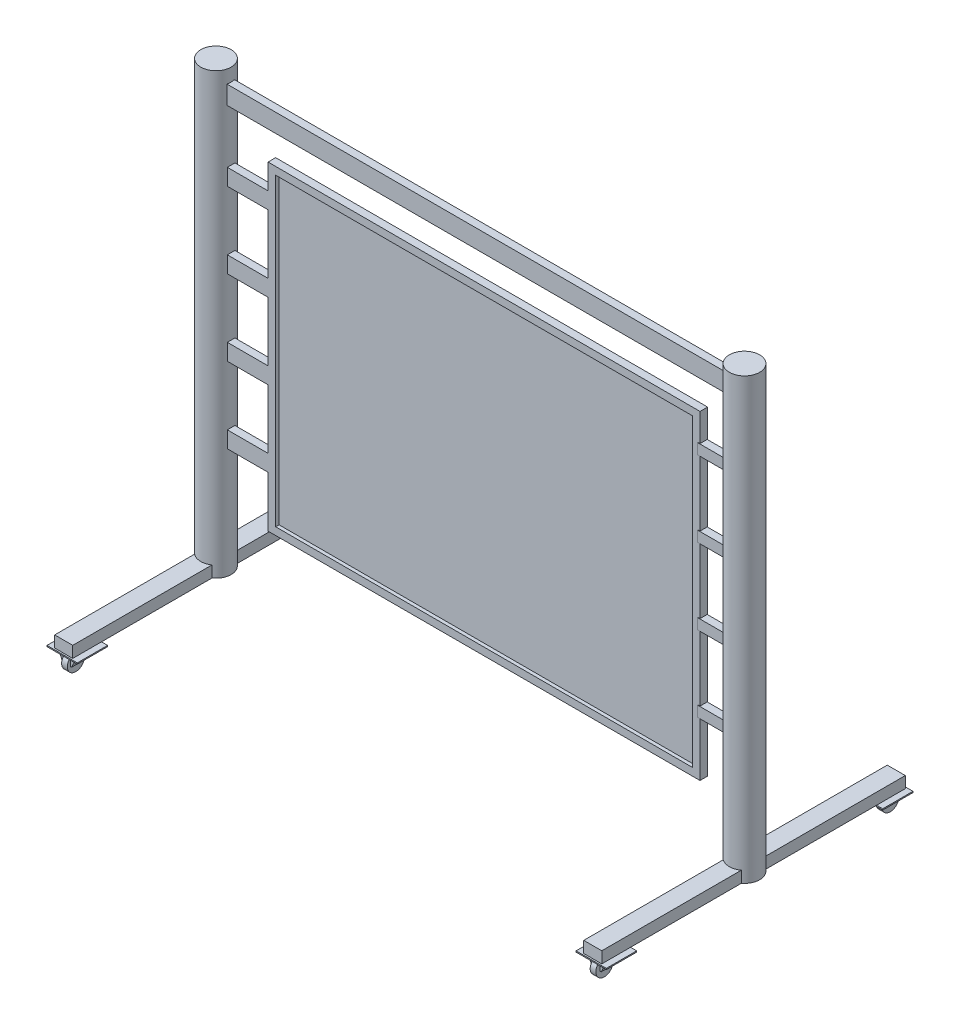
SolidWorks part; units mm, degrees
ref_plane "Alzado" through (0, 0, 0) normal (0, 0, 1) x (1, 0, 0)
ref_plane "Planta" through (0, 0, 0) normal (0, 1, 0) x (1, 0, 0)
ref_plane "Vista lateral" through (0, 0, 0) normal (1, 0, 0) x (0, 0, -1)
sketch "Croquis1" plane through (0, 0, 0) normal (0, 1, 0) x (1, 0, 0)
  line L0 (-40, 0) -> (1435, 0) construction
  circle A0 centre (0, 0) radius 40
  circle A1 centre (1395, 0) radius 40
  dimension "D1" = 80
  dimension "D2" = 80
  dimension "D3" = 1475
extrude "Saliente-Extruir1" add sketch "Croquis1" along normal blind 1160
sketch "Croquis2" plane through (0, 0, 0) normal (0, 0, 1) x (1, 0, 0)
  line L0 (0, 0) -> (0, 1160) construction
  line L1 (40, 1160) -> (-40, 1160) construction
  line L2 (0, 1160) -> (0, 580) construction
  line L3 (0, 580) -> (1435, 580) construction
  line L4 (1435, 0) -> (1435, 1160) construction
  line L5 (147.4875, 1001.8331) -> (147.4875, 158.1669)
  line L6 (167.4875, 981.8331) -> (1267.5125, 981.8331)
  line L7 (167.4875, 981.8331) -> (167.4875, 178.1669)
  line L8 (167.4875, 178.1669) -> (1267.5125, 178.1669)
  line L9 (1267.5125, 981.8331) -> (1267.5125, 178.1669)
  line L10 (147.4875, 158.1669) -> (1287.5125, 158.1669)
  line L11 (1287.5125, 1001.8331) -> (1287.5125, 158.1669)
  line L12 (147.4875, 1001.8331) -> (1287.5125, 1001.8331)
  point P5 (717.5, 580)
  dimension "D1" = 20
extrude "Saliente-Extruir2" add sketch "Croquis2" along normal blind 10 and the other way blind 10 separate body
sketch "Croquis3" plane through (0, 0, 0) normal (0, 0, 1) x (1, 0, 0)
  line L0 (40, 1101.4893) -> (1348.6676, 1101.4893) construction
  line L1 (40, 0) -> (40, 1160) construction
  line L2 (1348.6676, 1101.4893) -> (694.3338, 1101.4893) construction
  line L3 (1355, 1160) -> (1355, 0) construction
  line L4 (33.6676, 1125.7465) -> (1355, 1125.7465)
  line L5 (33.6676, 1125.7465) -> (33.6676, 1077.2322)
  line L6 (33.6676, 1077.2322) -> (1355, 1077.2322)
  line L7 (1355, 1125.7465) -> (1355, 1077.2322)
  line L8 (33.6676, 1125.7465) -> (1355, 1077.2322) construction
  line L9 (33.6676, 1077.2322) -> (1355, 1125.7465) construction
extrude "Saliente-Extruir3" add sketch "Croquis3" along normal blind 10 and the other way blind 10
sketch "Croquis4" plane through (0, 0, 0) normal (0, 0, 1) x (1, 0, 0)
  line L0 (167.4875, 580) -> (1267.5125, 580) construction
  line L1 (167.4875, 981.8331) -> (167.4875, 178.1669) construction
  line L2 (1267.5125, 178.1669) -> (1267.5125, 981.8331) construction
  line L3 (1267.5125, 580) -> (717.5, 580) construction
  line L4 (717.5, 580) -> (717.5, 981.8331) construction
  line L5 (1267.5125, 981.8331) -> (167.4875, 981.8331) construction
  line L7 (167.4875, 981.8331) -> (1267.5125, 981.8331)
  line L8 (167.4875, 981.8331) -> (167.4875, 178.1669)
  line L9 (167.4875, 178.1669) -> (1267.5125, 178.1669)
  line L10 (1267.5125, 981.8331) -> (1267.5125, 178.1669)
  line L11 (167.4875, 981.8331) -> (1267.5125, 178.1669) construction
  line L12 (167.4875, 178.1669) -> (1267.5125, 981.8331) construction
extrude "Saliente-Extruir4" add sketch "Croquis4" along normal blind 1
sketch "Croquis5" plane through (0, 0, 0) normal (0, 1, 0) x (1, 0, 0)
  line L0 (696.8649, -10) -> (696.8649, -155.1745) construction
  line L1 (1418.811, 400.5263) -> (1371.189, 400.5263)
  line L2 (1418.811, 400.5263) -> (1418.811, -400.5263)
  line L3 (1418.811, -400.5263) -> (1371.189, -400.5263)
  line L4 (1371.189, 400.5263) -> (1371.189, -400.5263)
  line L5 (1418.811, 400.5263) -> (1371.189, -400.5263) construction
  line L6 (1418.811, -400.5263) -> (1371.189, 400.5263) construction
  line L7 (1355, -10) -> (38.7298, -10) construction
  line L8 (-25.0811, -400.5263) -> (22.5408, 400.5263) construction
  line L9 (-25.0811, 400.5263) -> (22.5408, -400.5263) construction
  line L10 (22.5408, 400.5263) -> (22.5408, -400.5263)
  line L11 (-25.0811, -400.5263) -> (22.5408, -400.5263)
  line L12 (-25.0811, 400.5263) -> (-25.0811, -400.5263)
  line L13 (-25.0811, 400.5263) -> (22.5408, 400.5263)
  point P0 (1395, 0)
  point P14 (-1.2702, 0)
extrude "Saliente-Extruir5" add sketch "Croquis5" along normal blind 30
sketch "Croquis7" plane through (0, 0, 0) normal (0, 0, 1) x (1, 0, 0)
  line L0 (40, 914.3498) -> (147.4875, 914.3498) construction
  line L1 (40, 0) -> (40, 1077.2322) construction
  line L2 (147.4875, 1001.8331) -> (147.4875, 158.1669) construction
  line L3 (147.4875, 914.3498) -> (93.7438, 914.3498) construction
  line L5 (40, 935.9929) -> (147.4875, 935.9929)
  line L6 (40, 935.9929) -> (40, 892.7068)
  line L7 (40, 892.7068) -> (147.4875, 892.7068)
  line L8 (147.4875, 935.9929) -> (147.4875, 892.7068)
  line L9 (40, 935.9929) -> (147.4875, 892.7068) construction
  line L10 (40, 892.7068) -> (147.4875, 935.9929) construction
extrude "Saliente-Extruir6" add sketch "Croquis7" along normal blind 10 and the other way blind 10
pattern_linear "MatrizL1" count 4 spacing 200 along (0, -1, 0) of "Saliente-Extruir6"
sketch "Croquis11" plane through (0, 0, 1) normal (0, 0, 1) x (1, 0, 0)
  line L0 (147.4875, 935.9929) -> (147.4875, 892.7068)
  line L1 (147.4875, 892.7068) -> (147.4875, 935.9929)
  line L2 (147.4875, 914.3498) -> (1355, 914.3498)
  line L3 (1355, 1160) -> (1355, 0) construction
  line L4 (1355, 914.3498) -> (1282.1767, 914.3498)
  line L5 (1282.1767, 914.3498) -> (1318.5884, 914.3498)
  line L6 (1318.5884, 914.3498) -> (1318.5884, 1077.2322)
  line L7 (38.7298, 1077.2322) -> (1355, 1077.2322) construction
  line L9 (1282.1767, 928.3164) -> (1355, 928.3164)
  line L10 (1282.1767, 928.3164) -> (1282.1767, 900.3832)
  line L11 (1282.1767, 900.3832) -> (1355, 900.3832)
  line L12 (1355, 928.3164) -> (1355, 900.3832)
  line L13 (1282.1767, 928.3164) -> (1355, 900.3832) construction
  line L14 (1282.1767, 900.3832) -> (1355, 928.3164) construction
extrude "Saliente-Extruir8" add sketch "Croquis11" along normal blind 10 and the other way blind 10 contours L12 L4 L2 L10 L11 | L12 L9 L6 L4 | L9 L10 L2 L6 region at (1300.3825, 921.3331, 1) region at (1318.5884, 907.3665, 1) region at (1336.7942, 921.3331, 1)
pattern_linear "MatrizL3" count 4 spacing 200 along (0, -1, 0) of "Saliente-Extruir8"
sketch "Croquis12" plane through (0, 0, 0) normal (0, -1, 0) x (-1, 0, 0)
  line L0 (-1395, -400.5263) -> (-1395, -364.6522) construction
  line L1 (-1371.189, -400.5263) -> (-1418.811, -400.5263) construction
  line L2 (-22.5408, -48.2604) -> (25.0811, -48.2604) construction
  line L3 (-1355, -404.6522) -> (-1435, -404.6522)
  line L4 (-1355, -404.6522) -> (-1355, -324.6522)
  line L5 (-1355, -324.6522) -> (-1435, -324.6522)
  line L6 (-1435, -404.6522) -> (-1435, -324.6522)
  line L7 (-1355, -404.6522) -> (-1435, -324.6522) construction
  line L8 (-1355, -324.6522) -> (-1435, -404.6522) construction
  line L11 (-22.5408, -400.5263) -> (-22.5408, -33.0441) construction
  line L12 (25.0811, -31.1599) -> (25.0811, -400.5263) construction
  line L13 (25.0811, -48.2604) -> (1.2702, -48.2604) construction
  line L14 (1.2702, -48.2604) -> (1.2702, -120.2898) construction
  line L15 (-1371.189, -48.2604) -> (-1418.811, -48.2604) construction
  line L16 (-1371.189, -32.1409) -> (-1371.189, -400.5263) construction
  line L17 (-1418.811, -400.5263) -> (-1418.811, -32.1409) construction
  line L18 (-1418.811, -48.2604) -> (-1395, -48.2604) construction
  line L19 (-1395, -48.2604) -> (-1395, -144.8347) construction
  line L20 (1.2702, -120.2898) -> (-1395, -120.2898) construction
  line L21 (-1395, -120.2898) -> (-696.8649, -120.2898) construction
  line L22 (-696.8649, -120.2898) -> (-696.8649, -298.2426) construction
  line L23 (-38.7298, -324.6522) -> (41.2702, -404.6522) construction
  line L24 (-38.7298, -404.6522) -> (41.2702, -324.6522) construction
  line L25 (1.2702, -400.5263) -> (1.2702, -364.6522) construction
  line L26 (41.2702, -404.6522) -> (41.2702, -324.6522)
  line L27 (-38.7298, -324.6522) -> (41.2702, -324.6522)
  line L28 (-38.7298, -404.6522) -> (-38.7298, -324.6522)
  line L29 (-38.7298, -404.6522) -> (41.2702, -404.6522)
  line L30 (0, 0) -> (-1464.279, 0) construction
  line L31 (1.2702, 400.5263) -> (1.2702, 364.6522) construction
  line L32 (-38.7298, 404.6522) -> (41.2702, 324.6522) construction
  line L33 (-38.7298, 324.6522) -> (41.2702, 404.6522) construction
  line L34 (-1355, 324.6522) -> (-1435, 404.6522) construction
  line L35 (-1355, 404.6522) -> (-1435, 324.6522) construction
  line L36 (-1395, 400.5263) -> (-1395, 364.6522) construction
  line L37 (-38.7298, 404.6522) -> (41.2702, 404.6522)
  line L38 (-38.7298, 404.6522) -> (-38.7298, 324.6522)
  line L39 (-38.7298, 324.6522) -> (41.2702, 324.6522)
  line L40 (41.2702, 404.6522) -> (41.2702, 324.6522)
  line L41 (-1435, 404.6522) -> (-1435, 324.6522)
  line L42 (-1355, 324.6522) -> (-1435, 324.6522)
  line L43 (-1355, 404.6522) -> (-1355, 324.6522)
  line L44 (-1355, 404.6522) -> (-1435, 404.6522)
  dimension "D1" = 80
  dimension "D2" = 80
sketch "Croquis13" plane through (0, 0, 0) normal (0, -1, 0) x (-1, 0, 0)
  line L0 (25.0811, -38.6248) -> (-22.5408, -38.6248) construction
  line L1 (25.0811, -31.1599) -> (25.0811, -400.5263) construction
  line L2 (-22.5408, -400.5263) -> (-22.5408, -33.0441) construction
  line L3 (-22.5408, -38.6248) -> (1.2702, -38.6248) construction
  line L4 (1.2702, -38.6248) -> (-1418.811, -38.6248) construction
  line L5 (-1418.811, -400.5263) -> (-1418.811, -32.1409) construction
  line L6 (-1418.811, -38.6248) -> (-1371.189, -38.6248) construction
  line L7 (-1371.189, -32.1409) -> (-1371.189, -400.5263) construction
  line L8 (-1371.189, -38.6248) -> (-22.5408, -38.6248) construction
  line L9 (-22.5408, -38.6248) -> (-696.8649, -38.6248) construction
  line L10 (-696.8649, -38.6248) -> (-696.8649, -120.7287) construction
  line L11 (0, 0) -> (-1435, 0) construction
  arc A0 (-1418.811, 32.1409) -> (-1418.811, -32.1409) centre (-1395, 0) ccw construction
extrude "Saliente-Extruir10" add sketch "Croquis12" along normal blind 3
ref_plane "Plano1" through (-0.0811, 0, 0) normal (-1, 0, 0) x (0, 0, 1)
sketch "Croquis14" plane through (-0.0811, 0, 0) normal (-1, 0, 0) x (0, 0, 1)
  line L0 (0, 0) -> (0, -68.6636) construction
  circle A0 centre (-377.3085, -26.9423) radius 22.5
  circle A1 centre (377.3085, -26.9423) radius 22.5
  dimension "D1" = 45
extrude "Saliente-Extruir12" add sketch "Croquis14" along normal blind 7.5 and the other way blind 7.5 separate body
pattern_linear "MatrizL5" count 2 spacing 1395 along (1, 0, 0) of "Saliente-Extruir12"
ref_plane "Plano2" through (0, 0, -392.6522) normal (0, 0, -1) x (-1, 0, 0)
sketch "Croquis15" plane through (0, 0, -392.6522) normal (0, 0, -1) x (-1, 0, 0)
  line L0 (-1406.593, -29.6202) -> (-1419.2703, -3)
  line L2 (-1355, -3) -> (-1435, -3) construction
  line L3 (-1419.2703, -3) -> (-1372.2618, -3)
  line L4 (-1406.593, -29.6202) -> (-1403.281, -29.6202)
  line L5 (-1403.281, -29.6202) -> (-1403.281, -3)
  line L6 (-1403.281, -3) -> (-1386.2636, -3)
  line L7 (-1386.2636, -3) -> (-1386.2636, -29.6202)
  line L8 (-1386.2636, -29.6202) -> (-1382.5572, -29.6202)
  line L9 (-1382.5572, -29.6202) -> (-1372.2618, -3)
extrude "Saliente-Extruir13" add sketch "Croquis15" against normal blind 27.5 contours L4 L5 L3 L0 | L8 L9 L3 L7 region at (1381.3377, -13.7306, -392.6522) region at (1408.8002, -13.3961, -392.6522)
pattern_linear "MatrizL6" count 2 spacing 1395 along (-1, 0, 0) of "Saliente-Extruir13"
pattern_linear "MatrizL7" count 2 spacing 755 along (0, 0, 1) of "Saliente-Extruir13"
ref_plane "Plano3" through (0, 0, 392.6522) normal (0, 0, 1) x (1, 0, 0)
sketch "Croquis16" plane through (0, 0, 392.6522) normal (0, 0, 1) x (1, 0, 0)
  line L0 (-8.7364, -29.6202) -> (-12.4428, -29.6202)
  line L1 (-8.7364, -29.6202) -> (-12.4428, -29.6202) construction
  line L2 (-8.7364, -3) -> (-8.7364, -29.6202) construction
  line L3 (-12.4428, -29.6202) -> (-22.7382, -3)
  line L4 (-22.7382, -3) -> (-8.7364, -3)
  line L5 (-8.7364, -3) -> (-8.7364, -29.6202)
  line L6 (8.281, -29.6202) -> (11.593, -29.6202)
  line L7 (11.593, -29.6202) -> (24.2703, -3)
  line L8 (24.2703, -3) -> (8.281, -3)
  line L9 (8.281, -3) -> (8.281, -29.6202)
extrude "Saliente-Extruir14" add sketch "Croquis16" against normal blind 27.5
